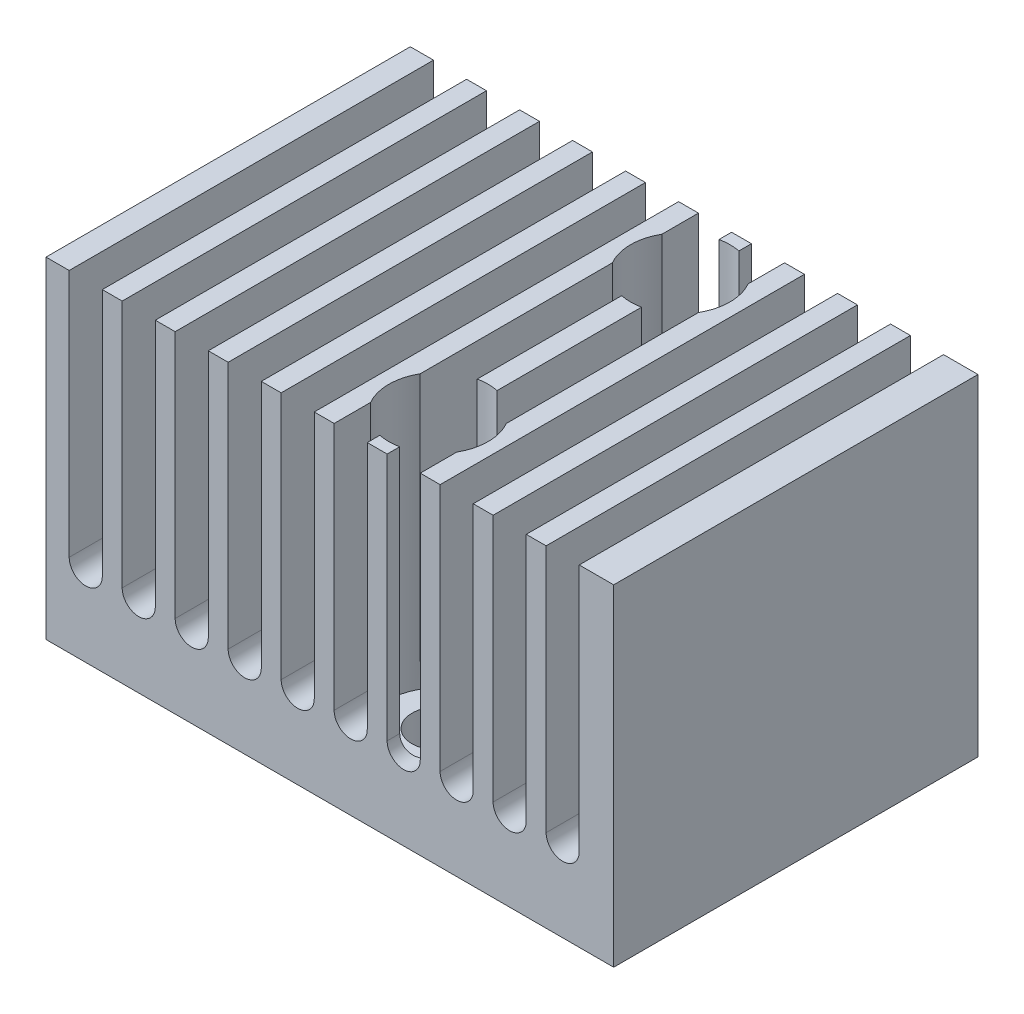
SolidWorks part; units mm, degrees
material "1060 合金"
ref_plane "前视基准面" through (0, 0, 0) normal (0, 0, 1) x (1, 0, 0)
ref_plane "上视基准面" through (0, 0, 0) normal (0, 1, 0) x (1, 0, 0)
ref_plane "右视基准面" through (0, 0, 0) normal (1, 0, 0) x (0, 0, -1)
sketch "草图1" plane through (0, 0, 0) normal (0, 1, 0) x (1, 0, 0)
  line L1 (-8.57, 5.5) -> (8.57, 5.5)
  line L2 (-8.57, 5.5) -> (-8.57, -5.5)
  line L3 (-8.57, -5.5) -> (8.57, -5.5)
  line L4 (8.57, 5.5) -> (8.57, -5.5)
  line L5 (-8.57, 5.5) -> (8.57, -5.5) construction
  line L6 (-8.57, -5.5) -> (8.57, 5.5) construction
  point P0 (0, 0)
  dimension "D1" = 11
  dimension "D2" = 17.14
extrude "凸台-拉伸1" add sketch "草图1" along normal blind 10
sketch "草图2" plane through (0, 0, 5.5) normal (0, 0, 1) x (1, 0, 0)
  line L0 (-8.57, 10) -> (8.57, 10) construction
  line L1 (-7.87, 10) -> (-6.87, 10)
  line L2 (-7.87, 10) -> (-7.87, 2.5)
  line L3 (-7.87, 2.5) -> (-6.87, 2.5)
  line L4 (-6.87, 10) -> (-6.87, 2.5)
  line L5 (-8.57, 10) -> (-8.57, 0) construction
  line L6 (-6.27, 10) -> (-6.27, 2.5)
  line L7 (-6.27, 10) -> (-5.27, 10)
  line L8 (-5.27, 10) -> (-5.27, 2.5)
  line L9 (-6.27, 2.5) -> (-5.27, 2.5)
  line L10 (-4.67, 10) -> (-4.67, 2.5)
  line L11 (-4.67, 10) -> (-3.67, 10)
  line L12 (-3.67, 10) -> (-3.67, 2.5)
  line L13 (-4.67, 2.5) -> (-3.67, 2.5)
  line L14 (-3.07, 10) -> (-3.07, 2.5)
  line L15 (-3.07, 10) -> (-2.07, 10)
  line L16 (-2.07, 10) -> (-2.07, 2.5)
  line L17 (-3.07, 2.5) -> (-2.07, 2.5)
  line L18 (-1.47, 10) -> (-1.47, 2.5)
  line L19 (-1.47, 10) -> (-0.47, 10)
  line L20 (-0.47, 10) -> (-0.47, 2.5)
  line L21 (-1.47, 2.5) -> (-0.47, 2.5)
  line L22 (0.13, 10) -> (0.13, 2.5)
  line L23 (0.13, 10) -> (1.13, 10)
  line L24 (1.13, 10) -> (1.13, 2.5)
  line L25 (0.13, 2.5) -> (1.13, 2.5)
  line L26 (1.73, 10) -> (1.73, 2.5)
  line L27 (1.73, 10) -> (2.73, 10)
  line L28 (2.73, 10) -> (2.73, 2.5)
  line L29 (1.73, 2.5) -> (2.73, 2.5)
  line L30 (3.33, 10) -> (3.33, 2.5)
  line L31 (3.33, 10) -> (4.33, 10)
  line L32 (4.33, 10) -> (4.33, 2.5)
  line L33 (3.33, 2.5) -> (4.33, 2.5)
  line L34 (4.93, 10) -> (4.93, 2.5)
  line L35 (4.93, 10) -> (5.93, 10)
  line L36 (5.93, 10) -> (5.93, 2.5)
  line L37 (4.93, 2.5) -> (5.93, 2.5)
  line L38 (6.53, 10) -> (6.53, 2.5)
  line L39 (6.53, 10) -> (7.53, 10)
  line L40 (7.53, 10) -> (7.53, 2.5)
  line L41 (6.53, 2.5) -> (7.53, 2.5)
  circle A0 centre (-7.37, 2.5) radius 0.5
  circle A1 centre (-5.77, 2.5) radius 0.5
  circle A2 centre (-4.17, 2.5) radius 0.5
  circle A3 centre (-2.57, 2.5) radius 0.5
  circle A4 centre (-0.97, 2.5) radius 0.5
  circle A5 centre (0.63, 2.5) radius 0.5
  circle A6 centre (2.23, 2.5) radius 0.5
  circle A7 centre (3.83, 2.5) radius 0.5
  circle A8 centre (5.43, 2.5) radius 0.5
  circle A9 centre (7.03, 2.5) radius 0.5
  line M8 (8.57, 10) -> (-8.57, 10)
  dimension "D1" = 1
  dimension "D2" = 7.5
  dimension "D3" = 0.7
  dimension "D4" = 10
extrude "切除-拉伸1" cut sketch "草图2" against normal through all contours A0 L4 L2 M8 | A1 L8 L6 M8 | L3 A0 | L3 A0 | L9 A1 | L9 A1 | A2 L12 L10 M8 | L13 A2 | L13 A2 | A3 L16 L14 M8 | L17 A3 | L17 A3 | A4 L20 L18 M8 | L21 A4 | L21 A4 | A5 L24 L22 M8 | L25 A5 | L25 A5 | A6 L28 L26 M8 | L29 A6 | L29 A6 | A7 L32 L30 M8 | L33 A7 | L33 A7 | A8 L36 L34 M8 | L37 A8 | L37 A8 | A9 L40 L38 M8 | L41 A9 | L41 A9 region at (7.03, 6.4455, 5.5) region at (5.43, 6.4455, 5.5) region at (3.83, 6.4455, 5.5) region at (2.23, 6.4455, 5.5) region at (0.63, 6.4455, 5.5) region at (-0.97, 6.4455, 5.5) region at (-2.57, 6.4455, 5.5) region at (-4.17, 6.4455, 5.5) region at (-5.77, 6.4455, 5.5) region at (-7.37, 6.4455, 5.5) region at (-7.37, 2.7122, 5.5) region at (-7.37, 2.2878, 5.5) region at (-5.77, 2.7122, 5.5) region at (-5.77, 2.2878, 5.5) region at (-4.17, 2.7122, 5.5) region at (-4.17, 2.2878, 5.5) region at (-2.57, 2.7122, 5.5) region at (-2.57, 2.2878, 5.5) region at (-0.97, 2.7122, 5.5) region at (-0.97, 2.2878, 5.5) region at (0.63, 2.7122, 5.5) region at (0.63, 2.2878, 5.5) region at (2.23, 2.7122, 5.5) region at (2.23, 2.2878, 5.5) region at (3.83, 2.7122, 5.5) region at (3.83, 2.2878, 5.5) region at (5.43, 2.7122, 5.5) region at (5.43, 2.2878, 5.5) region at (7.03, 2.7122, 5.5) region at (7.03, 2.2878, 5.5)
sketch "草图3" plane through (0, 0, 0) normal (0, -1, 0) x (1, 0, 0)
  line L0 (1.43, 5.5) -> (1.43, -5.5)
  line L1 (-8.57, 5.5) -> (8.57, 5.5) construction
  line L2 (8.57, -5.5) -> (-8.57, -5.5) construction
  line L3 (0, 0) -> (11.7843, 0) construction
  line L4 (8.57, 5.5) -> (8.57, -5.5) construction
  circle A0 centre (1.43, 3.65) radius 0.8
  circle A1 centre (1.43, -3.65) radius 0.8
  dimension "D2" = 1.6
  dimension "D1" = 7.14
  dimension "D3" = 3.65
extrude "切除-拉伸2" cut sketch "草图3" against normal blind 1.75 contours L0 A0 | L0 A0 | A1 L0 | A1 L0 region at (1.7695, 0, 3.65) region at (1.7695, 0, -3.65) region at (1.0905, 0, -3.65) region at (1.0905, 0, 3.65)
sketch "草图4" plane through (0, 1.75, 0) normal (0, -1, 0) x (1, 0, 0)
  circle A0 centre (1.43, 3.65) radius 1.5
  circle A1 centre (1.43, -3.65) radius 1.5
  dimension "D1" = 3
extrude "切除-拉伸3" cut sketch "草图4" against normal through all
